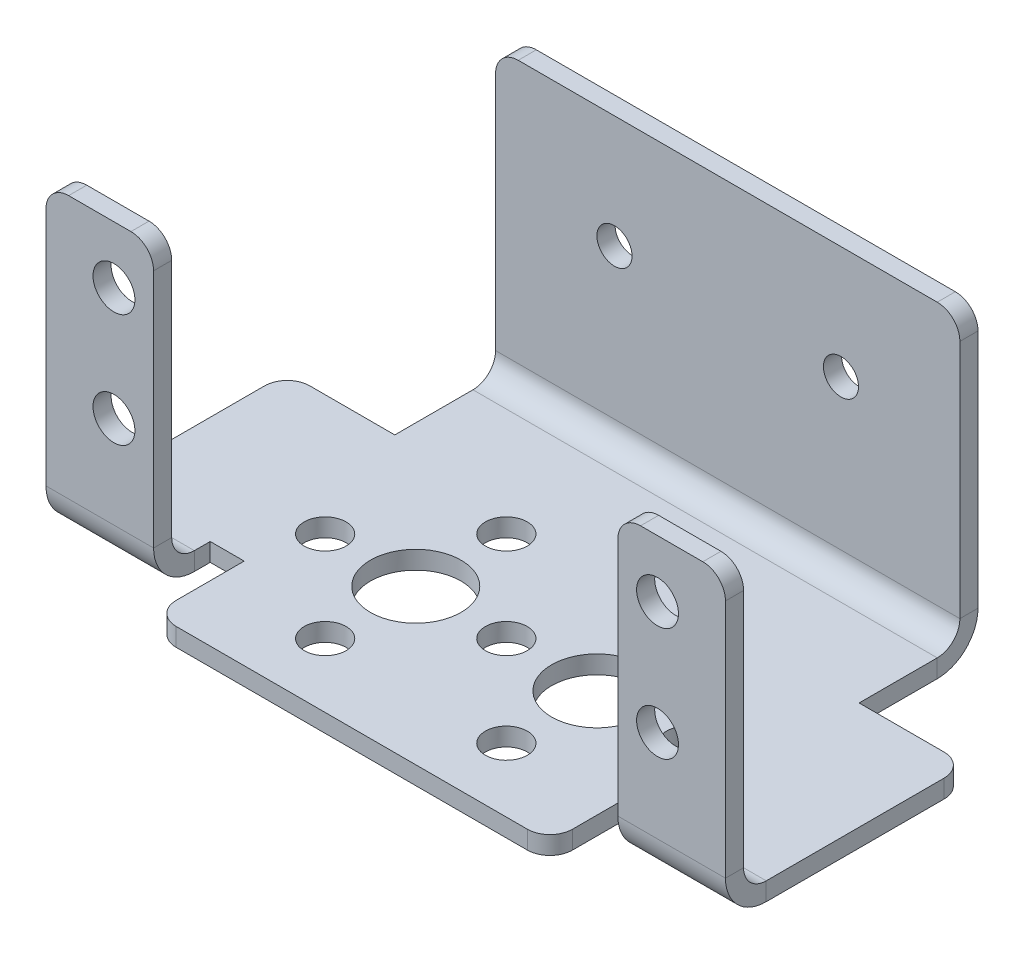
SolidWorks part; units mm, degrees
note: The reader was unsure of these and kept them because the rebuilt part matched: flange length of "Edge-Flange1".
other "Defeature"
material "5052-H34"
ref_plane "Front Plane" through (0, 0, 0) normal (0, 0, 1) x (1, 0, 0)
ref_plane "Top Plane" through (0, 0, 0) normal (0, 1, 0) x (1, 0, 0)
ref_plane "Right Plane" through (0, 0, 0) normal (1, 0, 0) x (0, 0, -1)
sketch "Sketch1" plane through (0, 0, 0) normal (0, 1, 0) x (1, 0, 0)
  line L0 (-20.5, 21.15) -> (20.5, 21.15)
  line L1 (20.5, 21.15) -> (20.5, 10.65)
  line L2 (20.5, 10.65) -> (30, 10.65)
  line L3 (30, 10.65) -> (30, -10.65)
  line L4 (30, -10.65) -> (20.5, -10.65)
  line L5 (20.5, -10.65) -> (20.5, -5.65)
  line L6 (20.5, -5.65) -> (17.5, -5.65)
  line L7 (17.5, -5.65) -> (17.5, -13.65)
  line L8 (17.5, -13.65) -> (-17.5, -13.65)
  line L9 (-17.5, -13.65) -> (-17.5, -5.65)
  line L10 (-17.5, -5.65) -> (-20.5, -5.65)
  line L11 (-20.5, -5.65) -> (-20.5, -10.65)
  line L12 (-20.5, -10.65) -> (-30, -10.65)
  line L13 (-30, -10.65) -> (-30, 10.65)
  line L14 (-30, 10.65) -> (-20.5, 10.65)
  line L15 (-20.5, 10.65) -> (-20.5, 21.15)
  point P3 (30, 0)
  point P18 (0, 21.15)
  dimension "D1" = 34.8
  dimension "D2" = 60
  dimension "D3" = 41
  dimension "D4" = 3
  dimension "D5" = 21.3
  dimension "D6" = 8
  dimension "D7" = 3
base flange "Base-Flange1" sketch "Sketch1" thickness 1.6 reverse thickness direction yes parameters "D1"=2
edge flange "Edge-Flange1" sketch "Sketch12" flange profiles "Sketch12", "Sketch13", "Sketch14" flange angle 90 flange length 26.8 flange position material inside bend radius 2 thickness 1.6 relief rectangular parameters "D6"=10, "D8"=1
sketch "Sketch12" plane through (0, 1.6, -21.15) normal (0, 0, -1) x (-1, 0, 0)
  line L2 (-20.5, 0) -> (-20.5, 25.2)
  line L3 (-20.5, 25.2) -> (20.5, 25.2)
  line L4 (20.5, 25.2) -> (20.5, 0)
  line L5 (-20.5, 0) -> (20.5, 0) construction
  line L6 (-20.5, 0) -> (20.5, 0)
sketch "Sketch13" plane through (0, 1.6, 10.65) normal (0, 0, 1) x (1, 0, 0)
  line L0 (20.5, 0) -> (30, 0) construction
  line L1 (20.5, 0) -> (30, 0)
  line L2 (20.5, 0) -> (20.5, 25.2)
  line L3 (20.5, 25.2) -> (30, 25.2)
  line L4 (30, 25.2) -> (30, 0)
sketch "Sketch14" plane through (0, 1.6, 10.65) normal (0, 0, 1) x (1, 0, 0)
  line L0 (-30, 0) -> (-20.5, 0) construction
  line L1 (-30, 0) -> (-20.5, 0)
  line L2 (-30, 0) -> (-30, 25.2)
  line L3 (-30, 25.2) -> (-20.5, 25.2)
  line L4 (-20.5, 25.2) -> (-20.5, 0)
bend "EdgeBend1" bend radius 2 bend angle 90 parameters "D5"=1
bend "EdgeBend2" bend radius 2 bend angle 90 parameters "D5"=2
bend "EdgeBend3" bend radius 2 bend angle 90 parameters "D5"=3
sketch "Sketch15" plane through (0, 1.6, 0) normal (0, 1, 0) x (1, 0, 0)
  circle A0 centre (0, 0) radius 1.85
  circle A1 centre (8, 0) radius 4
  circle A2 centre (-8, 0) radius 4
  circle A3 centre (16, 0) radius 1.85
  circle A4 centre (-16, 0) radius 1.85
  circle A5 centre (-8, 8) radius 1.85
  circle A6 centre (-8, -8) radius 1.85
  circle A7 centre (8, -8) radius 1.85
  circle A8 centre (8, 8) radius 1.85
  circle A9 centre (8, 0) radius 8 construction
  circle A10 centre (-8, 0) radius 8 construction
  dimension "D1" = 3.7
  dimension "D2" = 8
  dimension "D3" = 16
extrude "Cut-Extrude1" cut sketch "Sketch15" against normal up to next normal cut yes
sketch "Sketch16" plane through (0, 0, 10.65) normal (0, 0, 1) x (1, 0, 0)
  line L0 (0, 0) -> (0, 26.8) construction
  line L1 (-20.5, 26.8) -> (20.5, 26.8) construction
  line L3 (-20.5, 26.8) -> (-30, 26.8) construction
  circle A0 centre (-24, 21.75) radius 1.85
  circle A1 centre (-24, 11.75) radius 1.85
  circle A2 centre (24, 21.75) radius 1.85
  circle A3 centre (24, 11.75) radius 1.85
  point P14 (-24, 23.6)
  dimension "D1" = 3.7
  dimension "D2" = 48
  dimension "D3" = 3.2
  dimension "D4" = 10
extrude "Cut-Extrude2" cut sketch "Sketch16" against normal up to next normal cut yes
sketch "Sketch17" plane through (0, 0, -19.55) normal (0, 0, 1) x (1, 0, 0)
  line L0 (0, 0) -> (0, 26.8) construction
  line L1 (-20.5, 26.8) -> (20.5, 26.8) construction
  circle A0 centre (-10, 16.85) radius 1.55
  circle A1 centre (10, 16.85) radius 1.55
  point P9 (-10, 18.4)
  dimension "D1" = 3.1
  dimension "D2" = 8.4
  dimension "D3" = 20
extrude "Cut-Extrude3" cut sketch "Sketch17" against normal up to next normal cut yes
fillet "Fillet1" radius 2 10 edges at (20.5, 26.8, -20.35) (30, 26.8, 9.85) (-20.5, 26.8, -20.35) (20.5, 26.8, 9.85) (-20.5, 26.8, 9.85) (-30, 26.8, 9.85) (-30, 0.8, -10.65) (30, 0.8, -10.65) (17.5, 0.8, 13.65) (-17.5, 0.8, 13.65)
sketch "Bend-Lines1" [suppressed] plane through (0, 0, 0) normal (0, 1, 0) x (-1, 0, 0)
sketch "Bounding-Box1" [suppressed] plane through (0, 0, 0) normal (0, 1, 0) x (-1, 0, 0)
sheet metal parameters "Sheet-Metal1" thickness 1.6 parameters "D1"=2
flat pattern "Flat-Pattern1" [suppressed]
sketch "Bend-Lines2" plane through (0, 0, 0) normal (0, 1, 0) x (-1, 0, 0)
sketch "Bounding-Box2" [suppressed] plane through (0, 0, 0) normal (0, 1, 0) x (-1, 0, 0)
sheet metal parameters "Sheet-Metal2" thickness 1.6 parameters "D1"=2
flat pattern "Flat-Pattern1" [suppressed]
sketch "Bend-Lines2" plane through (0, 0, 0) normal (0, 1, 0) x (-1, 0, 0)
sketch "Bounding-Box2" [suppressed] plane through (0, 0, 0) normal (0, 1, 0) x (-1, 0, 0)
bend of the flat pattern "Flatten-<EdgeBend1>1"
bend of the flat pattern "Flatten-<EdgeBend2>1"
bend of the flat pattern "Flatten-<EdgeBend3>1"
sheet metal parameters "Sheet-Metal3" thickness 1.6 parameters "D1"=2
flat pattern "Flat-Pattern1" [suppressed]
sketch "Bend-Lines2" plane through (0, 0, 0) normal (0, 1, 0) x (-1, 0, 0)
sketch "Bounding-Box2" [suppressed] plane through (0, 0, 0) normal (0, 1, 0) x (-1, 0, 0)
bend of the flat pattern "Flatten-<EdgeBend1>1"
bend of the flat pattern "Flatten-<EdgeBend2>1"
bend of the flat pattern "Flatten-<EdgeBend3>1"
sheet metal parameters "Sheet-Metal4" thickness 1.6 parameters "D1"=2
flat pattern "Flat-Pattern1" [suppressed]
sketch "Bend-Lines2" plane through (0, 0, 0) normal (0, 1, 0) x (-1, 0, 0)
sketch "Bounding-Box2" [suppressed] plane through (0, 0, 0) normal (0, 1, 0) x (-1, 0, 0)
bend of the flat pattern "Flatten-<EdgeBend1>1"
bend of the flat pattern "Flatten-<EdgeBend2>1"
bend of the flat pattern "Flatten-<EdgeBend3>1"
sheet metal parameters "Sheet-Metal5" thickness 1.6 parameters "D1"=2
flat pattern "Flat-Pattern1"
sketch "Bend-Lines2" plane through (0, 0, 0) normal (0, -1, 0) x (-1, 0, 0)
  line L0 (20.5, -9.2491) -> (30, -9.2491) construction
  line L1 (-30, -9.2491) -> (-20.5, -9.2491) construction
  line L2 (20.5, 19.7491) -> (-20.5, 19.7491) construction
  line L3 (20.5, -9.2491) -> (30, -9.2491) construction
  line L4 (-30, -9.2491) -> (-20.5, -9.2491) construction
  line L5 (20.5, 19.7491) -> (-20.5, 19.7491) construction
sketch3d "Bounding-Box2" [suppressed]
  line L0 (-30, -34.6482, 0) -> (-30, 45.1482, 0) construction
  line L1 (30, -34.6482, 0) -> (30, 45.1482, 0) construction
  line L2 (-30, -34.6482, 0) -> (30, -34.6482, 0) construction
  line L3 (-30, 45.1482, 0) -> (30, 45.1482, 0) construction
bend of the flat pattern "Flatten-<EdgeBend1>1"
bend of the flat pattern "Flatten-<EdgeBend2>1"
bend of the flat pattern "Flatten-<EdgeBend3>1"
